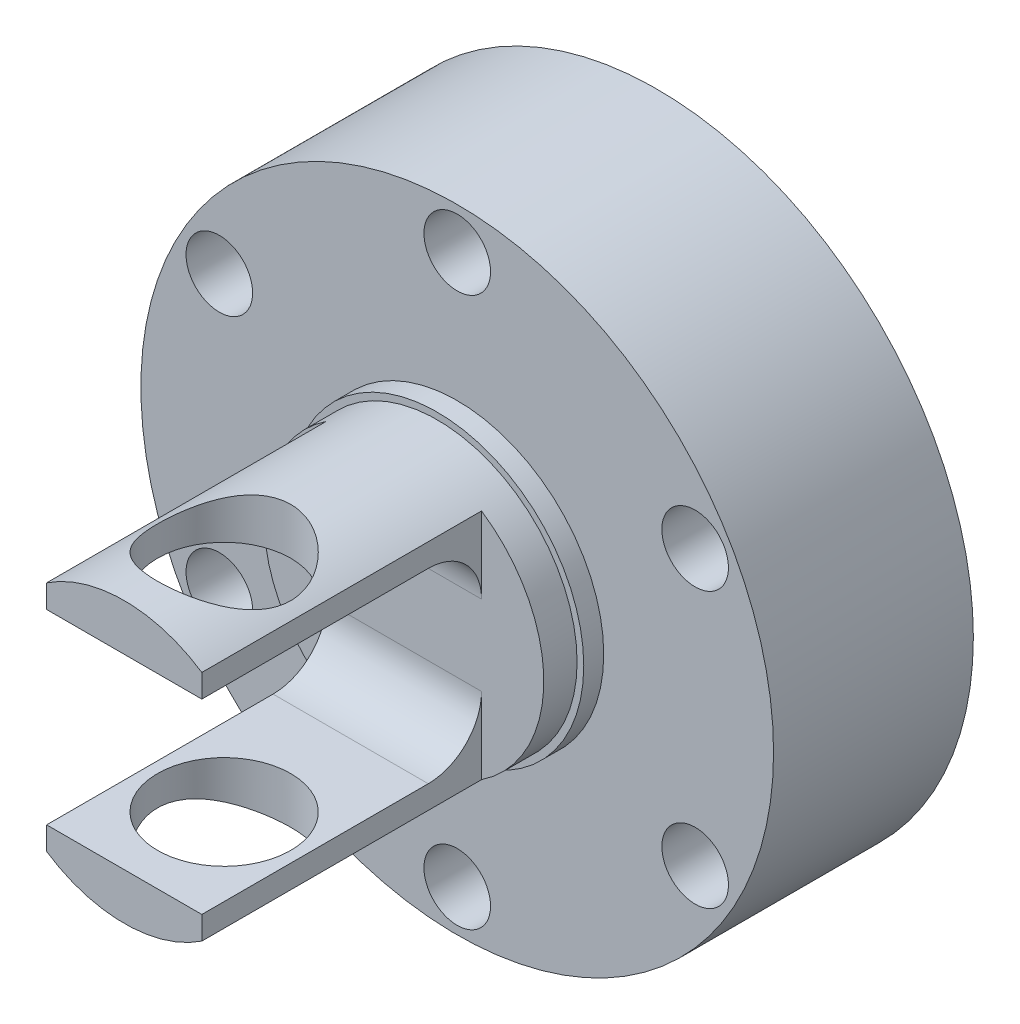
SolidWorks part; units mm, degrees
ref_plane "Płaszczyzna przednia" through (0, 0, 0) normal (0, 0, 1) x (1, 0, 0)
ref_plane "Płaszczyzna górna" through (0, 0, 0) normal (0, 1, 0) x (1, 0, 0)
ref_plane "Płaszczyzna prawa" through (0, 0, 0) normal (1, 0, 0) x (0, 0, -1)
sketch "Szkic1" plane through (0, 0, 0) normal (0, 0, 1) x (1, 0, 0)
  circle A0 centre (0, 0) radius 47.5
  dimension "D1" = 95
extrude "Dodanie-wyciągnięcie1" add sketch "Szkic1" along normal blind 30 contours A0
sketch "Szkic2" plane through (0, 0, 30) normal (0, 0, 1) x (1, 0, 0)
  circle A0 centre (0, 41.25) radius 5
  dimension "D1" = 10
  dimension "D2" = 41.25
extrude "Wytnij-wyciągnięcie1" cut sketch "Szkic2" against normal up to next
pattern_circular "Szyk kołowy1" count 6 over 360 about axis through (0, 0, 30) along (0, 0, 1) of "Wytnij-wyciągnięcie1"
sketch "Szkic3" plane through (0, 0, 30) normal (0, 0, 1) x (1, 0, 0)
  circle A0 centre (0, 0) radius 21
  dimension "D1" = 42
extrude "Dodanie-wyciągnięcie2" add sketch "Szkic3" along normal blind 0.001
sketch "Szkic4" plane through (0, 0, 30.001) normal (0, 0, 1) x (1, 0, 0)
  line L0 (-15.6525, 14) -> (15.6525, 14)
  line L1 (-15.6525, -14) -> (15.6525, -14)
  circle A1 centre (0, 0) radius 21 construction
  arc A2 (-15.6525, -14) -> (15.6525, -14) centre (0, 0) ccw
  arc A3 (15.6525, 14) -> (-15.6525, 14) centre (0, 0) ccw
  dimension "D1" = 14
  dimension "D2" = 14
extrude "Dodanie-wyciągnięcie3" add sketch "Szkic4" along normal blind 50
sketch "Szkic5" plane through (0, 0, 30.001) normal (0, 0, 1) x (1, 0, 0)
  circle A0 centre (0, 0) radius 22
  dimension "D1" = 44
extrude "Dodanie-wyciągnięcie4" add sketch "Szkic5" along normal blind 3
sketch "Szkic7" plane through (0, 0, 33.001) normal (0, 0, 1) x (1, 0, 0)
  circle A0 centre (0, 0) radius 21 construction
  circle A1 centre (0, 0) radius 21
extrude "Dodanie-wyciągnięcie5" add sketch "Szkic7" along normal blind 5
sketch "Szkic8" plane through (0, -14, 0) normal (0, 1, 0) x (1, 0, 0)
  line L0 (-15.6525, -80.001) -> (15.6525, -80.001) construction
  line L2 (15.6525, -80.001) -> (-15.6525, -80.001) construction
  circle A0 centre (0, -65.001) radius 10
  point P6 (0, -80.001)
  dimension "D1" = 20
  dimension "D2" = 15
extrude "Wytnij-wyciągnięcie2" cut sketch "Szkic8" against normal up to next and the other way through all
sketch "Szkic9" plane through (0, 0, 80.001) normal (0, 0, 1) x (1, 0, 0)
  line L0 (-11.6525, 14) -> (-11.6525, 17.4705)
  line L1 (-15.6525, 14) -> (15.6525, 14)
  line L2 (-15.6525, 14) -> (-11.6525, 14)
  line L3 (0, 16.8801) -> (0, 8.9496) construction
  line L4 (15.6525, 14) -> (11.6525, 14)
  line L5 (11.6525, 14) -> (11.6525, 17.4705)
  line L6 (0, 0) -> (11.8793, 0) construction
  line L7 (11.6525, -14) -> (11.6525, -17.4705)
  line L8 (15.6525, -14) -> (11.6525, -14)
  line L9 (-15.6525, -14) -> (-11.6525, -14)
  line L10 (-11.6525, -14) -> (-11.6525, -17.4705)
  arc A0 (11.6525, 17.4705) -> (15.6525, 14) centre (0, 0) cw
  arc A1 (15.6525, 14) -> (-15.6525, 14) centre (0, 0) ccw
  arc A2 (-11.6525, 17.4705) -> (-15.6525, 14) centre (0, 0) ccw
  arc A3 (11.6525, -17.4705) -> (15.6525, -14) centre (0, 0) ccw
  arc A4 (-11.6525, -17.4705) -> (-15.6525, -14) centre (0, 0) cw
  dimension "D2" = 4
  dimension "D1" = 0
extrude "Wytnij-wyciągnięcie3" cut sketch "Szkic9" against normal up to surface (42 mm away) up to face at (0, 0, 38.001)
fillet "Zaokrąglenie1" radius 8 2 edges at (0, -14, 38.001) (0, 14, 38.001)
